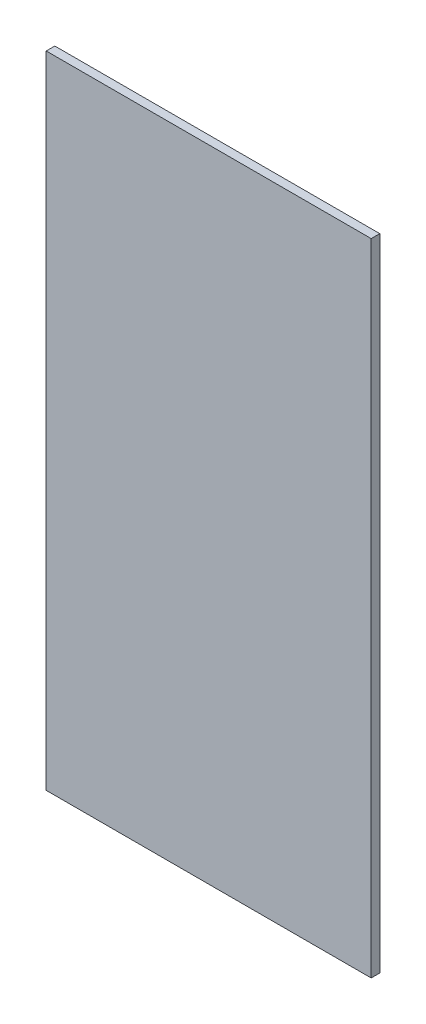
SolidWorks part; units mm, degrees
ref_plane "Front Plane" through (0, 0, 0) normal (1, 0, 0) x (0, 1, 0)
ref_plane "Top Plane" through (0, 0, 0) normal (0, 0, 1) x (0, 1, 0)
ref_plane "Right Plane" through (0, 0, 0) normal (0, 1, 0) x (-1, 0, 0)
sketch "Sketch1" plane through (0, 0, 0) normal (0, 0, 1) x (0, 1, 0)
  line L1 (-60, -30.45) -> (60, -30.45)
  line L2 (-60, -30.45) -> (-60, 30.45)
  line L3 (-60, 30.45) -> (60, 30.45)
  line L4 (60, -30.45) -> (60, 30.45)
  line L5 (-60, -30.45) -> (60, 30.45) construction
  line L6 (-60, 30.45) -> (60, -30.45) construction
  point P0 (0, 0)
  dimension "D1" = 120
  dimension "D2" = 60.9
extrude "Boss-Extrude1" add sketch "Sketch1" along normal blind 1.61
